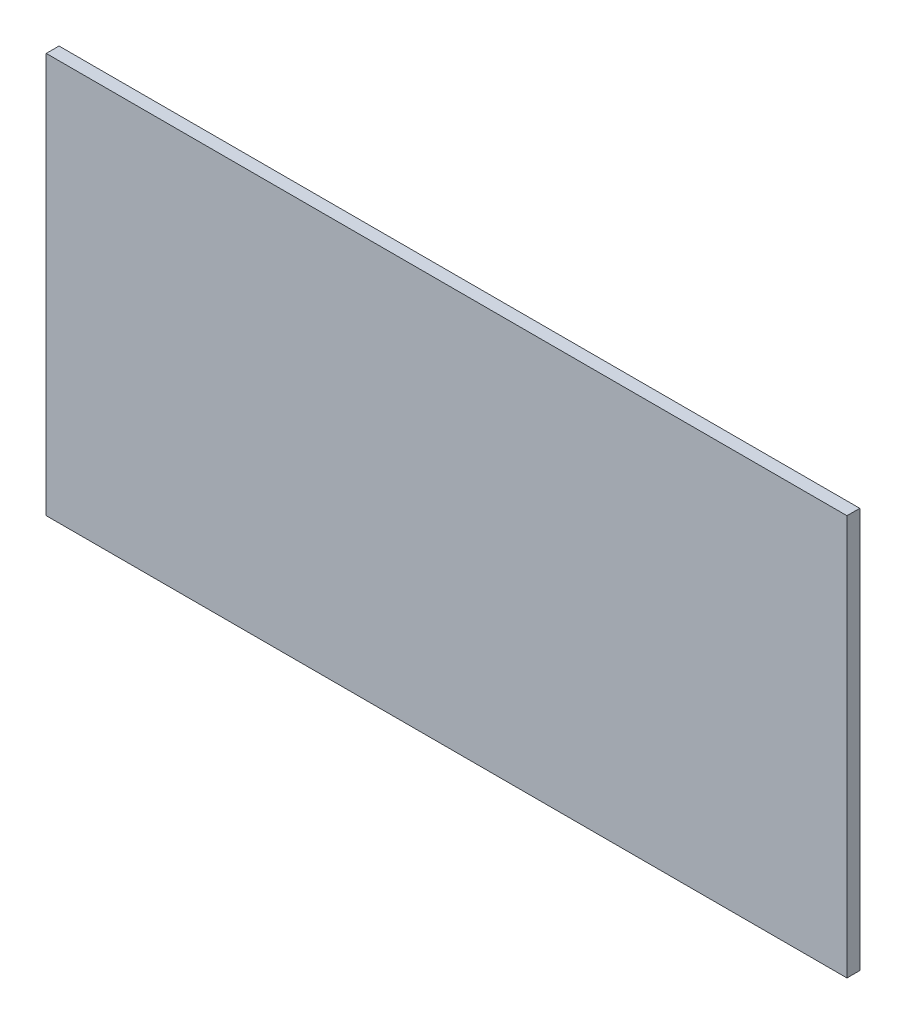
SolidWorks part; units mm, degrees
ref_plane "Ebene vorne" through (0, 0, 0) normal (0, 0, 1) x (1, 0, 0)
ref_plane "Ebene oben" through (0, 0, 0) normal (0, 1, 0) x (1, 0, 0)
ref_plane "Ebene rechts" through (0, 0, 0) normal (1, 0, 0) x (0, 0, -1)
sketch "Skizze1" plane through (0, 0, 0) normal (0, 0, 1) x (1, 0, 0)
  line L1 (0, 125) -> (250, 125)
  line L2 (0, 125) -> (0, 0)
  line L3 (0, 0) -> (250, 0)
  line L4 (250, 125) -> (250, 0)
  point P4 (0, 0)
  dimension "D1" = 250
  dimension "D2" = 125
extrude "Aufsatz-Linear austragen1" add sketch "Skizze1" along normal blind 4 contours L2 L1 L4 L3
